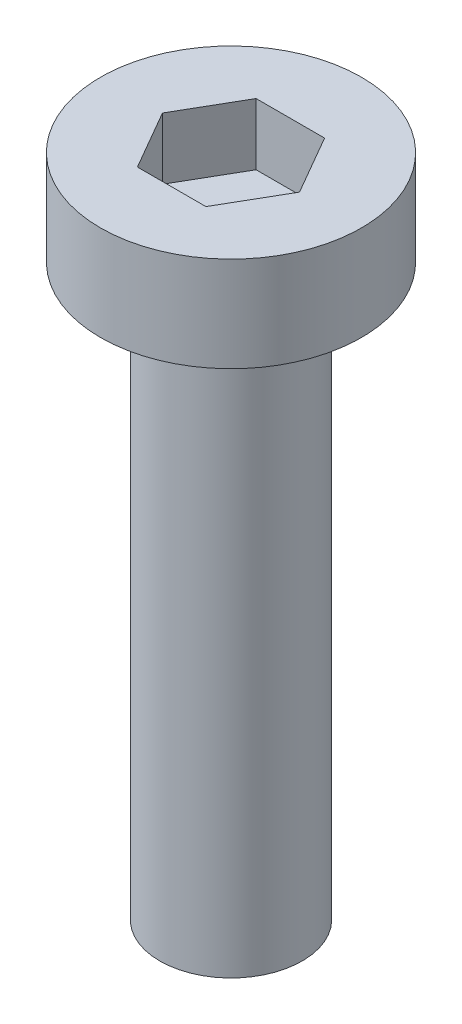
SolidWorks part; units mm, degrees
material "普通碳钢"
ref_plane "前视基准面" through (0, 0, 0) normal (0, 0, 1) x (1, 0, 0)
ref_plane "上视基准面" through (0, 0, 0) normal (0, 1, 0) x (1, 0, 0)
ref_plane "右视基准面" through (0, 0, 0) normal (1, 0, 0) x (0, 0, -1)
sketch "草图1" plane through (0, 0, 0) normal (0, 1, 0) x (1, 0, 0)
  circle A0 centre (0, 0) radius 1.5
  circle A1 centre (0, 0) radius 2.75
  dimension "公称直径" = 3
  dimension "外径" = 5.5
extrude "头部高" add sketch "草图1" along normal blind 2 contours A0 | A1 A0 region at (0, 0, 0) region at (-2.6722, 0, 0)
extrude "公称长度" add sketch "草图1<3>" against normal blind 12 contours A0 region at (0, 0, 0)
sketch "草图1<3>" plane through (0, 0, 0) normal (0, 1, 0) x (1, 0, 0) same geometry as "草图1"
sketch "草图2" plane through (0, 2, 0) normal (0, 1, 0) x (1, 0, 0)
  line L1 (1.4434, 0) -> (0.7217, 1.25)
  line L2 (0.7217, 1.25) -> (-0.7217, 1.25)
  line L3 (-0.7217, 1.25) -> (-1.4434, 0)
  line L4 (-1.4434, 0) -> (-0.7217, -1.25)
  line L5 (-0.7217, -1.25) -> (0.7217, -1.25)
  line L6 (0.7217, -1.25) -> (1.4434, 0)
  circle A0 centre (0, 0) radius 1.25 construction
  dimension "D1" = 2.5
extrude "切除-拉伸1" cut sketch "草图2" against normal blind 1.3
